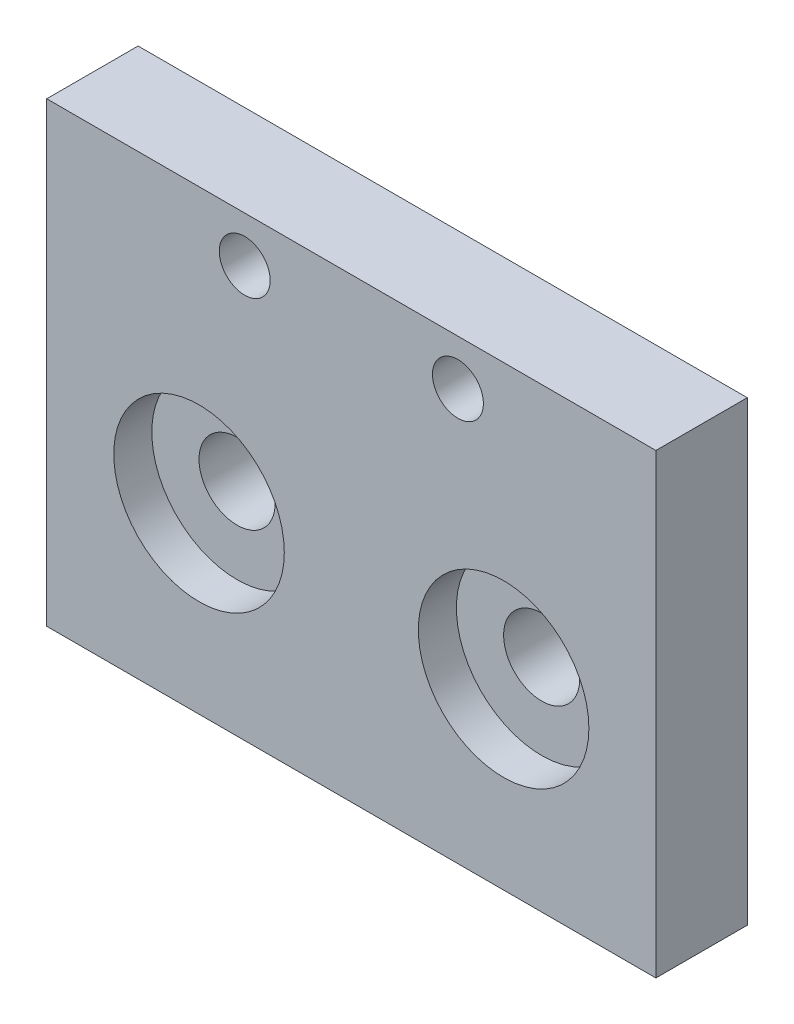
SolidWorks part; units mm, degrees
ref_plane "Front Plane" through (0, 0, 0) normal (0, 0, 1) x (1, 0, 0)
ref_plane "Top Plane" through (0, 0, 0) normal (0, 1, 0) x (1, 0, 0)
ref_plane "Right Plane" through (0, 0, 0) normal (1, 0, 0) x (0, 0, -1)
sketch "Sketch1" plane through (0, 0, 0) normal (0, 0, 1) x (1, 0, 0)
  line L0 (31.75, -9.525) -> (-31.75, -9.525) construction
  line L1 (-31.75, 0) -> (31.75, 0)
  line L2 (-31.75, 0) -> (-31.75, -47.625)
  line L3 (-31.75, -47.625) -> (31.75, -47.625)
  line L4 (31.75, 0) -> (31.75, -47.625)
  line L5 (31.75, -9.525) -> (31.75, 0) construction
  line L6 (0, -9.525) -> (0, -47.625) construction
  circle A0 centre (11.1125, -4.7625) radius 2.1 construction
  circle A1 centre (-11.1125, -4.7625) radius 2.1 construction
  circle A2 centre (11.1125, -4.7625) radius 2.1 construction
  circle A3 centre (-11.1125, -4.7625) radius 2.1 construction
  circle A4 centre (-11.1125, -4.7625) radius 2.6543
  circle A5 centre (11.1125, -4.7625) radius 2.6543
  circle A8 centre (-15.875, -28.575) radius 3.9687
  circle A9 centre (-15.875, -28.575) radius 8.89
  circle A10 centre (-171.45, -17.4815) radius 3.9687 construction
  circle A11 centre (-171.45, -17.4815) radius 8.89 construction
  circle A12 centre (15.875, -28.575) radius 3.9687
  circle A13 centre (15.875, -28.575) radius 8.89
  point P23 (0, -28.575)
  dimension "D2" = 5.3086
  dimension "D3" = 38.1
  dimension "D1" = 47.625
  dimension "D4" = 31.75
extrude "Boss-Extrude1" add sketch "Sketch1" along normal blind 9.525 contours L4 L1 L2 L3 A9 A5 A4 A13 | A9 A8 | A13 A12 region at (0, -23.1998, 0) region at (-24.5136, -28.575, 0) region at (7.2364, -28.575, 0)
extrude "Cut-Extrude2" cut sketch "Sketch1<3>" against normal offset from surface 5.5575 and the other way through all from surface contours A9 A8 | A13 A12 region at (-24.5136, -28.575, 0) region at (7.2364, -28.575, 0) up to face at (13.7668, -4.7625, 0) starting at face at (13.7668, -4.7625, 9.525)
sketch "Sketch1<3>" plane through (0, 0, 0) normal (0, 0, 1) x (1, 0, 0) same geometry as "Sketch1"
